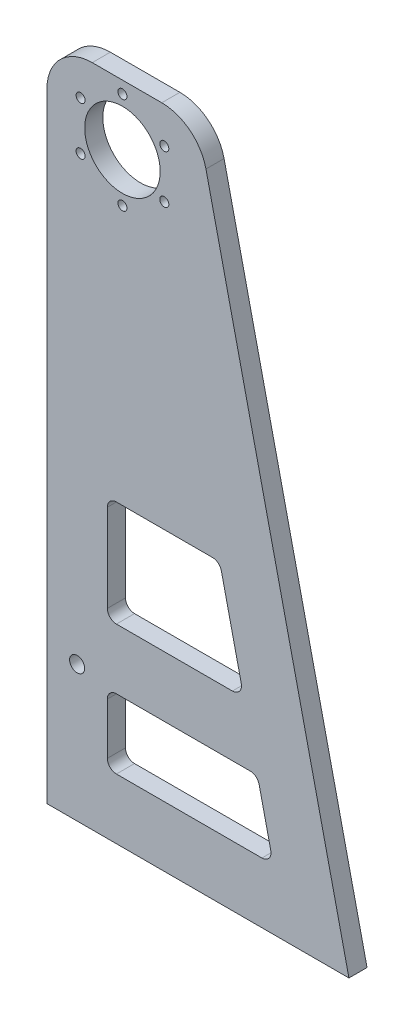
SolidWorks part; units mm, degrees
ref_plane "Plano frontal" through (0, 0, 0) normal (0, 0, 1) x (1, 0, 0)
ref_plane "Plano superior" through (0, 0, 0) normal (0, 1, 0) x (1, 0, 0)
ref_plane "Plano direito" through (0, 0, 0) normal (1, 0, 0) x (0, 0, -1)
sketch "Esboço1" plane through (0, 0, 0) normal (0, 0, 1) x (1, 0, 0)
  line L0 (0, 0) -> (0, 220)
  line L2 (100, 0) -> (0, 0)
  line L3 (0, 220) -> (50, 220)
  line L4 (50, 220) -> (100, 0)
  line L5 (10, 75.5) -> (10, 15) construction
  line L6 (25, 220) -> (25, 180) construction
  line L7 (10, 15) -> (85.7122, 15) construction
  line L8 (85.7122, 15) -> (71.9622, 75.5) construction
  line L9 (71.9622, 75.5) -> (10, 75.5) construction
  line L10 (20, 95) -> (20, 66)
  line L11 (23, 63) -> (61.4135, 63)
  line L12 (64.3389, 66.6649) -> (57.748, 95.6649)
  line L13 (54.8226, 98) -> (23, 98)
  line L14 (20, 40) -> (20, 23)
  line L15 (23, 20) -> (71.1862, 20)
  line L16 (74.1116, 23.6649) -> (70.248, 40.6649)
  line L17 (23, 43) -> (67.3226, 43)
  circle A0 centre (25, 200) radius 12.5
  circle A1 centre (25, 200) radius 16 construction
  circle A2 centre (25, 216) radius 1.5
  arc A8 (70.248, 40.6649) -> (67.3226, 43) centre (67.3226, 40) ccw
  arc A9 (71.1862, 20) -> (74.1116, 23.6649) centre (71.1862, 23) ccw
  arc A10 (20, 23) -> (23, 20) centre (23, 23) ccw
  arc A11 (20, 40) -> (23, 43) centre (23, 40) cw
  arc A12 (57.748, 95.6649) -> (54.8226, 98) centre (54.8226, 95) ccw
  arc A13 (61.4135, 63) -> (64.3389, 66.6649) centre (61.4135, 66) ccw
  arc A14 (20, 66) -> (23, 63) centre (23, 66) ccw
  arc A15 (20, 95) -> (23, 98) centre (23, 95) cw
  circle A16 centre (38.8564, 208) radius 1.5
  circle A17 centre (38.8564, 192) radius 1.5
  circle A18 centre (25, 184) radius 1.5
  circle A19 centre (11.1436, 192) radius 1.5
  circle A20 centre (11.1436, 208) radius 1.5
  circle A21 centre (10, 45) radius 2.5
  point P26 (22.5, 105)
  point P49 (20, 63)
  point P55 (25, 175)
  point P56 (25, 200)
  dimension "D3" = 20
  dimension "D4" = 25
  dimension "D6" = 32
  dimension "D7" = 3
  dimension "D21" = 3
  dimension "D15" = 10
  dimension "D16" = 45
  dimension "D17" = 5
  dimension "D1" = 220
  dimension "D2" = 100
  dimension "D5" = 50
  dimension "D9" = 25
  dimension "D10" = 6
  dimension "D11" = 20
  dimension "D12" = 20
  dimension "D13" = 15
  dimension "D14" = 20
  dimension "D18" = 10
  dimension "D20" = 20
  dimension "D22" = 23
  dimension "D8" = 35
extrude "Ressalto-extrusão2" add sketch "Esboço1" along normal blind 6
fillet "Filete1" radius 15 2 edges at (0, 220, 3) (50, 220, 3)
